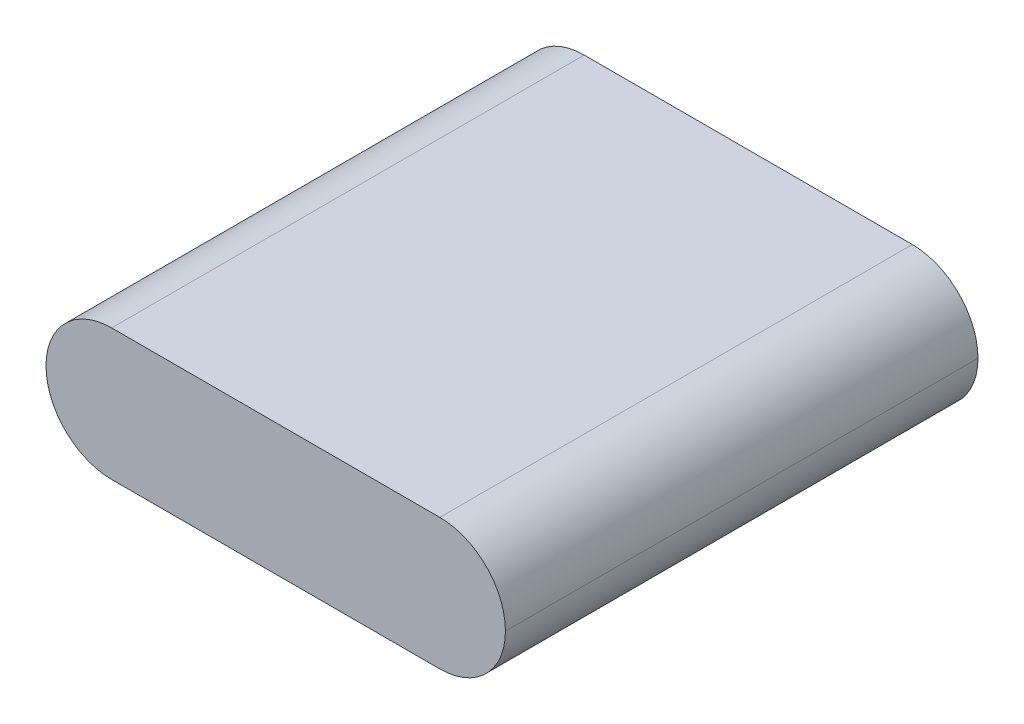
SolidWorks part; units mm, degrees
ref_plane "Front" through (0, 0, 0) normal (0, 0, 1) x (1, 0, 0)
ref_plane "Top" through (0, 0, 0) normal (0, 1, 0) x (1, 0, 0)
ref_plane "Right" through (0, 0, 0) normal (1, 0, 0) x (0, 0, -1)
sketch "Sketch1" plane through (0, 0, 0) normal (0, 1, 0) x (1, 0, 0)
  line L1 (0, 0) -> (70, 0)
  line L2 (0, 0) -> (0, 72)
  line L3 (0, 72) -> (70, 72)
  line L4 (70, 0) -> (70, 72)
extrude "Boss-Extrude1" add sketch "Sketch1" along normal blind 20
fillet "Fillet1" radius 10 4 edges at (0, 0, -36) (70, 0, -36) (70, 20, -36) (0, 20, -36)
